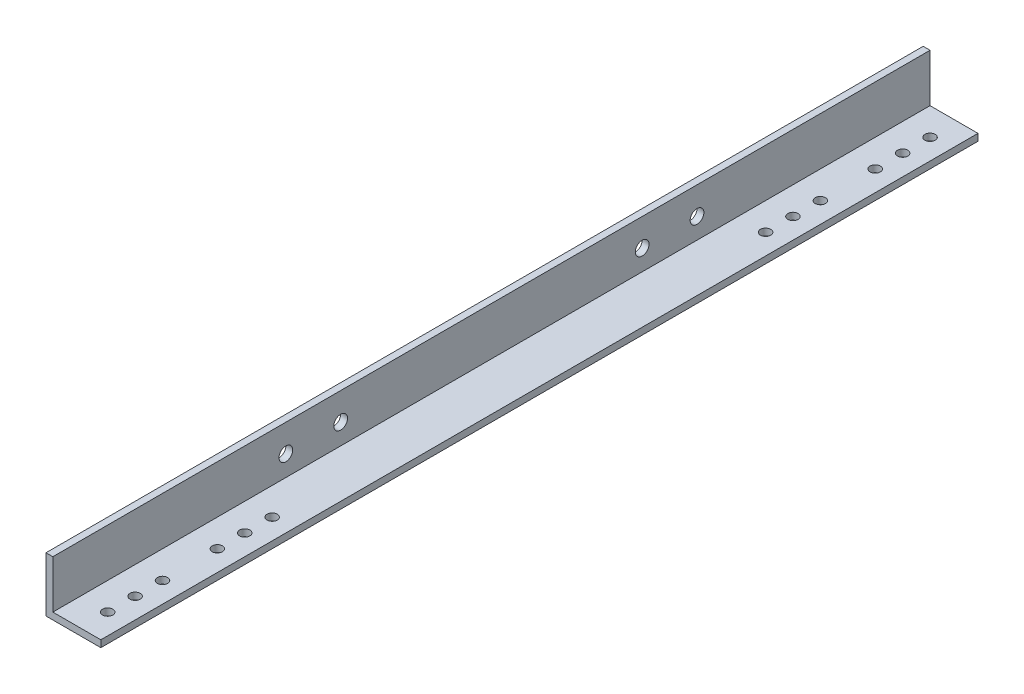
SolidWorks part; units mm, degrees
ref_plane "Front Plane" through (0, 0, 0) normal (0, 0, 1) x (1, 0, 0)
ref_plane "Top Plane" through (0, 0, 0) normal (0, 1, 0) x (1, 0, 0)
ref_plane "Right Plane" through (0, 0, 0) normal (1, 0, 0) x (0, 0, -1)
sketch "Sketch1" plane through (0, 0, 0) normal (0, 0, 1) x (1, 0, 0)
  line L0 (0, 0) -> (25.4, 0)
  line L1 (25.4, 0) -> (25.4, 3.175)
  line L2 (25.4, 3.175) -> (3.175, 3.175)
  line L3 (3.175, 3.175) -> (3.175, 25.4)
  line L4 (3.175, 25.4) -> (0, 25.4)
  line L5 (0, 25.4) -> (0, 0)
  dimension "D1" = 25.4
  dimension "D2" = 25.4
  dimension "D3" = 3.175
  dimension "D4" = 3.175
extrude "Boss-Extrude1" add sketch "Sketch1" along normal blind 406.4
sketch "Sketch2" plane through (0, 3.175, 0) normal (0, 1, 0) x (1, 0, 0)
  line L0 (25.4, -406.4) -> (3.175, -406.4) construction
  line L1 (3.175, -355.6) -> (25.4, -355.6)
  line L2 (3.175, -406.4) -> (3.175, 0) construction
  line L3 (25.4, -406.4) -> (25.4, 0) construction
  line L4 (3.175, -203.2) -> (25.4, -203.2)
  line L5 (3.175, -50.8) -> (25.4, -50.8)
  circle A0 centre (15.875, -393.7) radius 2.3813
  circle A1 centre (15.875, -381) radius 2.3813
  circle A2 centre (15.875, -368.3) radius 2.3813
  circle A3 centre (15.875, -317.5) radius 2.3813
  circle A4 centre (15.875, -330.2) radius 2.3813
  circle A5 centre (15.875, -342.9) radius 2.3813
  circle A6 centre (15.875, -12.7) radius 2.3813
  circle A7 centre (15.875, -25.4) radius 2.3813
  circle A8 centre (15.875, -38.1) radius 2.3813
  circle A9 centre (15.875, -63.5) radius 2.3813
  circle A10 centre (15.875, -76.2) radius 2.3813
  circle A11 centre (15.875, -88.9) radius 2.3813
  dimension "D1" = 4.7625
  dimension "D5" = 4.7625
  dimension "D6" = 4.7625
  dimension "D2" = 12.7
  dimension "D3" = 12.7
  dimension "D4" = 12.7
  dimension "D7" = 50.8
  dimension "D8" = 12.7
extrude "Cut-Extrude1" cut sketch "Sketch2" against normal through all contours A0 | A2 | A1 | A5 | A4 | A3 | A11 | A10 | A9 | A8 | A7 | A6 region at (15.875, 3.175, 393.7) region at (15.875, 3.175, 381) region at (15.875, 3.175, 368.3) region at (15.875, 3.175, 317.5) region at (15.875, 3.175, 330.2) region at (15.875, 3.175, 342.9) region at (15.875, 3.175, 12.7) region at (15.875, 3.175, 25.4) region at (15.875, 3.175, 38.1) region at (15.875, 3.175, 63.5) region at (15.875, 3.175, 76.2) region at (15.875, 3.175, 88.9)
sketch "Sketch3" plane through (0, 0, 0) normal (-1, 0, 0) x (0, 0, 1)
  line L0 (406.4, 25.4) -> (0, 25.4) construction
  line L1 (203.2, 25.4) -> (203.2, 0)
  line L2 (406.4, 0) -> (0, 0) construction
  line L3 (0, 25.4) -> (0, 0) construction
  circle A0 centre (107.95, 12.7) radius 3.175
  circle A1 centre (133.35, 12.7) radius 3.175
  circle A4 centre (273.05, 12.7) radius 3.175
  circle A5 centre (298.45, 12.7) radius 3.175
  circle A6 centre (273.05, 12.7) radius 3.175
  circle A7 centre (298.45, 12.7) radius 3.175
  point P15 (203.2, 25.4)
  dimension "D2" = 12.7
  dimension "D1" = 6.35
  dimension "D4" = 6.35
  dimension "D6" = 25.4
  dimension "D8" = 69.85
  dimension "D9" = 12.7
  dimension "D3" = 107.95
extrude "Cut-Extrude2" cut sketch "Sketch3" against normal through all contours A0 | A1 | A7 | A6 | A4 | A5 region at (0, 12.7, 107.95) region at (0, 12.7, 133.35) region at (0, 12.7, 273.05) region at (0, 12.7, 298.45)
equation "\"D5@Sketch2\"=\"D1@Sketch2\""
equation "\"D6@Sketch2\"=\"D1@Sketch2\""
equation "\"D2@Sketch3\"=\"D9@Sketch3\""
